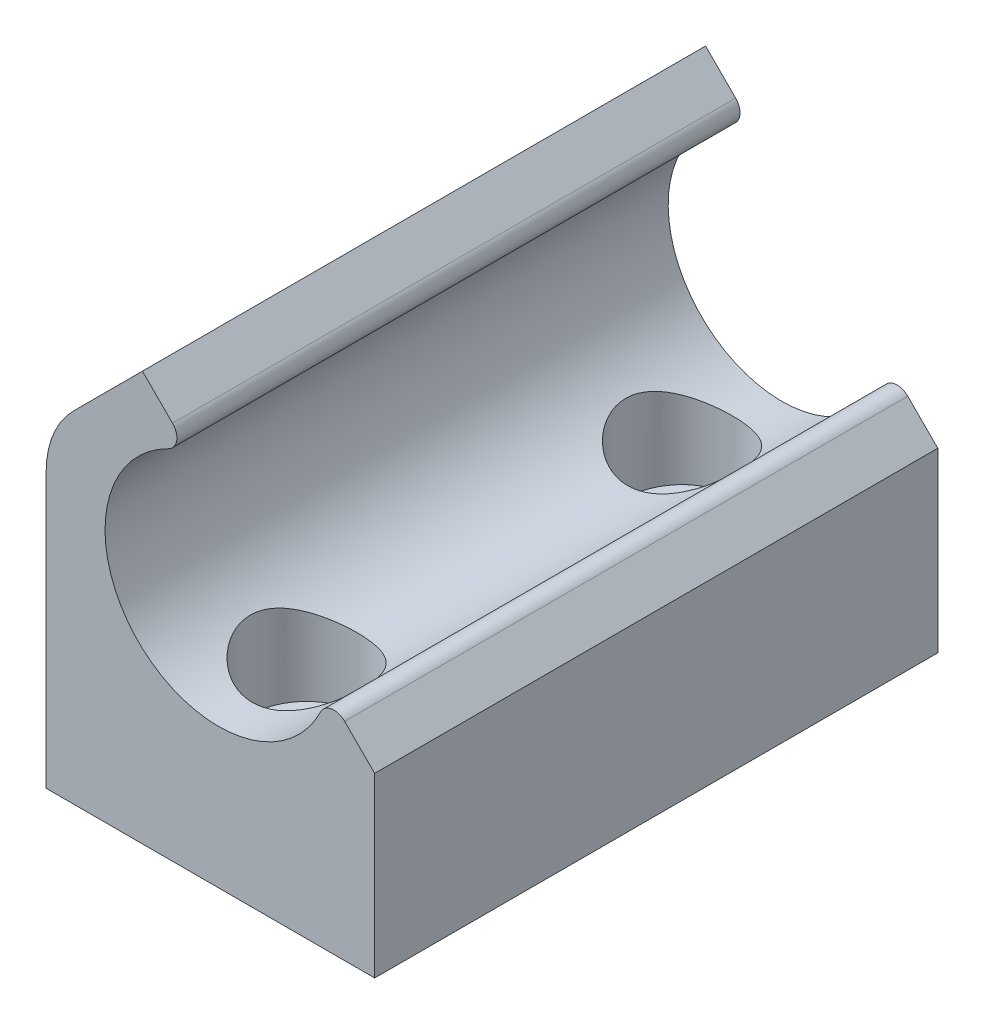
SolidWorks part; units mm, degrees
ref_plane "Front Plane" through (0, 0, 0) normal (0, 0, 1) x (1, 0, 0)
ref_plane "Top Plane" through (0, 0, 0) normal (0, 1, 0) x (1, 0, 0)
ref_plane "Right Plane" through (0, 0, 0) normal (1, 0, 0) x (0, 0, -1)
sketch "Sketch1" plane through (0, 0, 0) normal (0, 0, 1) x (1, 0, 0)
  line L0 (0, 0) -> (17.5, 0)
  line L1 (17.5, 0) -> (17.5, 9.44)
  line L2 (17.5, 9.44) -> (15.0251, 11.9149)
  line L3 (7.6032, 19.3368) -> (5.1283, 21.8117)
  line L4 (5.1283, 21.8117) -> (0, 16.6833)
  line L5 (0, 16.6833) -> (0, 0)
  arc A0 (15.0251, 11.9149) -> (7.6032, 19.3368) centre (9.1858, 13.4974) cw
  dimension "D1" = 6.05
  dimension "D2" = 3.5
  dimension "D3" = 17.5
  dimension "D4" = 9.44
  dimension "D5" = 3.01
  dimension "D6" = 45
extrude "Boss-Extrude1" add sketch "Sketch1" along normal blind 30
fillet "Fillet1" radius 0.8 2 edges at (15.0251, 11.9149, 15) (7.6032, 19.3368, 15)
ref_plane "Plane1" through (0, 10.8284, 0) normal (0, -1, 0) x (-1, 0, 0)
sketch "Sketch3" plane through (0, 10.8284, 0) normal (0, -1, 0) x (-1, 0, 0)
  line L0 (-3.1358, 0) -> (-14.6152, 0) construction
  line L1 (-3.1358, 0) -> (-14.6152, 0) construction
  circle A0 centre (-8.8755, -5) radius 3
  circle A1 centre (-8.8755, -25) radius 3
  point P7 (-8.8755, 0)
  dimension "D1" = 6
  dimension "D2" = 5
  dimension "D3" = 20
extrude "Cut-Extrude1" cut sketch "Sketch3" along normal blind 7
sketch "Sketch4" plane through (0, 10.8284, 0) normal (0, -1, 0) x (-1, 0, 0)
  circle A0 centre (-8.8755, -5) radius 1.55
  circle A1 centre (-8.8755, -25) radius 1.55
  dimension "D1" = 3.1
  dimension "D2" = 3.1
extrude "Cut-Extrude2" cut sketch "Sketch4" along normal through all
fillet "Fillet2" radius 5 1 edges at (0, 16.6833, 15)
